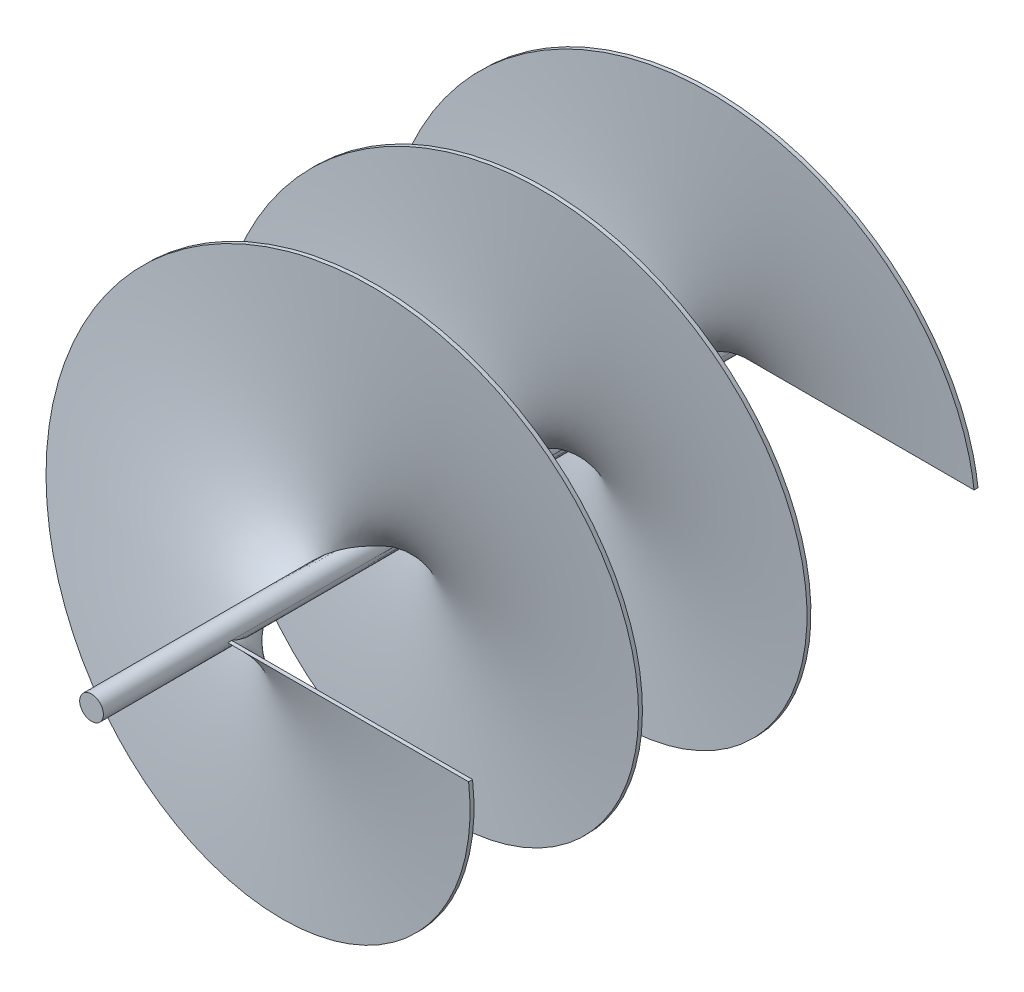
SolidWorks part; units mm, degrees
material "Plain Carbon Steel"
ref_plane "Front Plane" through (0, 0, 0) normal (0, 0, 1) x (1, 0, 0)
ref_plane "Top Plane" through (0, 0, 0) normal (0, 1, 0) x (1, 0, 0)
ref_plane "Right Plane" through (0, 0, 0) normal (1, 0, 0) x (0, 0, -1)
sketch "Sketch1" plane through (0, 0, 0) normal (0, 0, 1) x (1, 0, 0)
  circle A0 centre (0, 0) radius 9.525
  dimension "D1" = 19.05
extrude "Boss-Extrude1" add sketch "Sketch1" along normal blind 609.6
ref_plane "Plane1" through (0, 0, 508) normal (0, 0, 1) x (1, 0, 0)
sketch "Sketch2" plane through (0, 0, 508) normal (0, 0, 1) x (1, 0, 0)
  circle A0 centre (0, 0) radius 203.2
  dimension "D1" = 406.4
curve "Helix/Spiral1" pitch 135.4667 height 406.4 radius 203.2 centre (0, 0, 508) axis (0, 0, -1) start towards (1, 0, 0)
sketch "Sketch3" plane through (0, 0, 0) normal (0, 1, 0) x (1, 0, 0)
  line L0 (-9.525, 0) -> (-9.525, -609.6) construction
  line L1 (-9.525, -509.5875) -> (203.2, -509.5875)
  line L2 (-9.525, -509.5875) -> (-9.525, -506.4125)
  line L3 (-9.525, -506.4125) -> (203.2, -506.4125)
  line L4 (203.2, -509.5875) -> (203.2, -506.4125)
  spline S0 degree 3 poles (-795.7118, -553.8828) (-91.6333, -551.3817) (233.2801, -527.8361) (199.5403, -503.7221) (194.5854, -501.5831) (187.717, -499.4442) (179.0025, -497.3053) (168.5276, -495.1663) (156.3954, -493.0274) (142.7252, -490.8884) (127.6515, -488.7495) (111.3223, -486.6105) (93.8984, -484.4716) (75.5511, -482.3326) (56.4608, -480.1937) (36.8153, -478.0547) (16.8077, -475.9158) (-3.3652, -473.7768) (-23.505, -471.6379) (-43.4136, -469.4989) (-62.8953, -467.36) (-81.7585, -465.2211) (-99.8177, -463.0821) (-116.8952, -460.9432) (-132.8231, -458.8042) (-147.4449, -456.6653) (-160.6166, -454.5263) (-172.2088, -452.3874) (-182.1075, -450.2484) (-190.2153, -448.1095) (-196.4524, -445.9705) (-200.7577, -443.8316) (-203.0886, -441.6926) (-203.4223, -439.5537) (-201.7555, -437.4147) (-198.1047, -435.2758) (-192.5056, -433.1368) (-185.0134, -430.9979) (-175.7017, -428.8589) (-164.6621, -426.72) (-152.0033, -424.5811) (-137.8496, -422.4421) (-122.3402, -420.3032) (-105.6277, -418.1642) (-87.8765, -416.0253) (-69.2611, -413.8863) (-49.9645, -411.7474) (-30.1766, -409.6084) (-10.092, -407.4695) (10.092, -405.3305) (30.1766, -403.1916) (49.9645, -401.0526) (69.2611, -398.9137) (87.8765, -396.7747) (105.6277, -394.6358) (122.3402, -392.4968) (137.8496, -390.3579) (152.0033, -388.2189) (164.6621, -386.08) (175.7017, -383.9411) (185.0134, -381.8021) (192.5056, -379.6632) (198.1047, -377.5242) (201.7555, -375.3853) (203.4223, -373.2463) (203.0886, -371.1074) (200.7577, -368.9684) (196.4524, -366.8295) (190.2153, -364.6905) (182.1075, -362.5516) (172.2088, -360.4126) (160.6166, -358.2737) (147.4449, -356.1347) (132.8231, -353.9958) (116.8952, -351.8568) (99.8177, -349.7179) (81.7585, -347.5789) (62.8953, -345.44) (43.4136, -343.3011) (23.505, -341.1621) (3.3652, -339.0232) (-16.8077, -336.8842) (-36.8153, -334.7453) (-56.4608, -332.6063) (-75.5511, -330.4674) (-93.8984, -328.3284) (-111.3223, -326.1895) (-127.6515, -324.0505) (-142.7252, -321.9116) (-156.3954, -319.7726) (-168.5276, -317.6337) (-179.0025, -315.4947) (-187.717, -313.3558) (-194.5854, -311.2168) (-199.5403, -309.0779) (-202.5328, -306.9389) (-203.5336, -304.8) (-202.5328, -302.6611) (-199.5403, -300.5221) (-194.5854, -298.3832) (-187.717, -296.2442) (-179.0025, -294.1053) (-168.5276, -291.9663) (-156.3954, -289.8274) (-142.7252, -287.6884) (-127.6515, -285.5495) (-111.3223, -283.4105) (-93.8984, -281.2716) (-75.5511, -279.1326) (-56.4608, -276.9937) (-36.8153, -274.8547) (-16.8077, -272.7158) (3.3652, -270.5768) (23.505, -268.4379) (43.4136, -266.2989) (62.8953, -264.16) (81.7585, -262.0211) (99.8177, -259.8821) (116.8952, -257.7432) (132.8231, -255.6042) (147.4449, -253.4653) (160.6166, -251.3263) (172.2088, -249.1874) (182.1075, -247.0484) (190.2153, -244.9095) (196.4524, -242.7705) (200.7577, -240.6316) (203.0886, -238.4926) (203.4223, -236.3537) (201.7555, -234.2147) (198.1047, -232.0758) (192.5056, -229.9368) (185.0134, -227.7979) (175.7017, -225.6589) (164.6621, -223.52) (152.0033, -221.3811) (137.8496, -219.2421) (122.3402, -217.1032) (105.6277, -214.9642) (87.8765, -212.8253) (69.2611, -210.6863) (49.9645, -208.5474) (30.1766, -206.4084) (10.092, -204.2695) (-10.092, -202.1305) (-30.1766, -199.9916) (-49.9645, -197.8526) (-69.2611, -195.7137) (-87.8765, -193.5747) (-105.6277, -191.4358) (-122.3402, -189.2968) (-137.8496, -187.1579) (-152.0033, -185.0189) (-164.6621, -182.88) (-175.7017, -180.7411) (-185.0134, -178.6021) (-192.5056, -176.4632) (-198.1047, -174.3242) (-201.7555, -172.1853) (-203.4223, -170.0463) (-203.0886, -167.9074) (-200.7577, -165.7684) (-196.4524, -163.6295) (-190.2153, -161.4905) (-182.1075, -159.3516) (-172.2088, -157.2126) (-160.6166, -155.0737) (-147.4449, -152.9347) (-132.8231, -150.7958) (-116.8952, -148.6568) (-99.8177, -146.5179) (-81.7585, -144.3789) (-62.8953, -142.24) (-43.4136, -140.1011) (-23.505, -137.9621) (-3.3652, -135.8232) (16.8077, -133.6842) (36.8153, -131.5453) (56.4608, -129.4063) (75.5511, -127.2674) (93.8984, -125.1284) (111.3223, -122.9895) (127.6515, -120.8505) (142.7252, -118.7116) (156.3954, -116.5726) (168.5276, -114.4337) (179.0025, -112.2947) (187.717, -110.1558) (194.5854, -108.0169) (199.5403, -105.8779) (233.2791, -81.7646) (-91.612, -58.2198) (-795.6403, -55.7175) knots -0.162231 -0.162231 -0.162231 -0.162231 0.005263 0.010526 0.015789 0.021053 0.026316 0.031579 0.036842 0.042105 0.047368 0.052632 0.057895 0.063158 0.068421 0.073684 0.078947 0.084211 0.089474 0.094737 0.1 0.105263 0.110526 0.115789 0.121053 0.126316 0.131579 0.136842 0.142105 0.147368 0.152632 0.157895 0.163158 0.168421 0.173684 0.178947 0.184211 0.189474 0.194737 0.2 0.205263 0.210526 0.215789 0.221053 0.226316 0.231579 0.236842 0.242105 0.247368 0.252632 0.257895 0.263158 0.268421 0.273684 0.278947 0.284211 0.289474 0.294737 0.3 0.305263 0.310526 0.315789 0.321053 0.326316 0.331579 0.336842 0.342105 0.347368 0.352632 0.357895 0.363158 0.368421 0.373684 0.378947 0.384211 0.389474 0.394737 0.4 0.405263 0.410526 0.415789 0.421053 0.426316 0.431579 0.436842 0.442105 0.447368 0.452632 0.457895 0.463158 0.468421 0.473684 0.478947 0.484211 0.489474 0.494737 0.5 0.505263 0.510526 0.515789 0.521053 0.526316 0.531579 0.536842 0.542105 0.547368 0.552632 0.557895 0.563158 0.568421 0.573684 0.578947 0.584211 0.589474 0.594737 0.6 0.605263 0.610526 0.615789 0.621053 0.626316 0.631579 0.636842 0.642105 0.647368 0.652632 0.657895 0.663158 0.668421 0.673684 0.678947 0.684211 0.689474 0.694737 0.7 0.705263 0.710526 0.715789 0.721053 0.726316 0.731579 0.736842 0.742105 0.747368 0.752632 0.757895 0.763158 0.768421 0.773684 0.778947 0.784211 0.789474 0.794737 0.8 0.805263 0.810526 0.815789 0.821053 0.826316 0.831579 0.836842 0.842105 0.847368 0.852632 0.857895 0.863158 0.868421 0.873684 0.878947 0.884211 0.889474 0.894737 0.9 0.905263 0.910526 0.915789 0.921053 0.926316 0.931579 0.936842 0.942105 0.947368 0.952632 0.957895 0.963158 0.968421 0.973684 0.978947 0.984211 0.989474 0.994737 1.162226 1.162226 1.162226 1.162226 only from (203.2, -508) to (203.2, -101.6) construction
  spline S1 degree 3 poles (203.2, -508) (203.2, -507.2873) (202.5328, -505.8609) (199.5403, -503.7221) (194.5854, -501.5831) (187.717, -499.4442) (179.0025, -497.3053) (168.5276, -495.1663) (156.3954, -493.0274) (142.7252, -490.8884) (127.6515, -488.7495) (111.3223, -486.6105) (93.8984, -484.4716) (75.5511, -482.3326) (56.4608, -480.1937) (36.8153, -478.0547) (16.8077, -475.9158) (-3.3652, -473.7768) (-23.505, -471.6379) (-43.4136, -469.4989) (-62.8953, -467.36) (-81.7585, -465.2211) (-99.8177, -463.0821) (-116.8952, -460.9432) (-132.8231, -458.8042) (-147.4449, -456.6653) (-160.6166, -454.5263) (-172.2088, -452.3874) (-182.1075, -450.2484) (-190.2153, -448.1095) (-196.4524, -445.9705) (-200.7577, -443.8316) (-203.0886, -441.6926) (-203.4223, -439.5537) (-201.7555, -437.4147) (-198.1047, -435.2758) (-192.5056, -433.1368) (-185.0134, -430.9979) (-175.7017, -428.8589) (-164.6621, -426.72) (-152.0033, -424.5811) (-137.8496, -422.4421) (-122.3402, -420.3032) (-105.6277, -418.1642) (-87.8765, -416.0253) (-69.2611, -413.8863) (-49.9645, -411.7474) (-30.1766, -409.6084) (-10.092, -407.4695) (10.092, -405.3305) (30.1766, -403.1916) (49.9645, -401.0526) (69.2611, -398.9137) (87.8765, -396.7747) (105.6277, -394.6358) (122.3402, -392.4968) (137.8496, -390.3579) (152.0033, -388.2189) (164.6621, -386.08) (175.7017, -383.9411) (185.0134, -381.8021) (192.5056, -379.6632) (198.1047, -377.5242) (201.7555, -375.3853) (203.4223, -373.2463) (203.0886, -371.1074) (200.7577, -368.9684) (196.4524, -366.8295) (190.2153, -364.6905) (182.1075, -362.5516) (172.2088, -360.4126) (160.6166, -358.2737) (147.4449, -356.1347) (132.8231, -353.9958) (116.8952, -351.8568) (99.8177, -349.7179) (81.7585, -347.5789) (62.8953, -345.44) (43.4136, -343.3011) (23.505, -341.1621) (3.3652, -339.0232) (-16.8077, -336.8842) (-36.8153, -334.7453) (-56.4608, -332.6063) (-75.5511, -330.4674) (-93.8984, -328.3284) (-111.3223, -326.1895) (-127.6515, -324.0505) (-142.7252, -321.9116) (-156.3954, -319.7726) (-168.5276, -317.6337) (-179.0025, -315.4947) (-187.717, -313.3558) (-194.5854, -311.2168) (-199.5403, -309.0779) (-202.5328, -306.9389) (-203.5336, -304.8) (-202.5328, -302.6611) (-199.5403, -300.5221) (-194.5854, -298.3832) (-187.717, -296.2442) (-179.0025, -294.1053) (-168.5276, -291.9663) (-156.3954, -289.8274) (-142.7252, -287.6884) (-127.6515, -285.5495) (-111.3223, -283.4105) (-93.8984, -281.2716) (-75.5511, -279.1326) (-56.4608, -276.9937) (-36.8153, -274.8547) (-16.8077, -272.7158) (3.3652, -270.5768) (23.505, -268.4379) (43.4136, -266.2989) (62.8953, -264.16) (81.7585, -262.0211) (99.8177, -259.8821) (116.8952, -257.7432) (132.8231, -255.6042) (147.4449, -253.4653) (160.6166, -251.3263) (172.2088, -249.1874) (182.1075, -247.0484) (190.2153, -244.9095) (196.4524, -242.7705) (200.7577, -240.6316) (203.0886, -238.4926) (203.4223, -236.3537) (201.7555, -234.2147) (198.1047, -232.0758) (192.5056, -229.9368) (185.0134, -227.7979) (175.7017, -225.6589) (164.6621, -223.52) (152.0033, -221.3811) (137.8496, -219.2421) (122.3402, -217.1032) (105.6277, -214.9642) (87.8765, -212.8253) (69.2611, -210.6863) (49.9645, -208.5474) (30.1766, -206.4084) (10.092, -204.2695) (-10.092, -202.1305) (-30.1766, -199.9916) (-49.9645, -197.8526) (-69.2611, -195.7137) (-87.8765, -193.5747) (-105.6277, -191.4358) (-122.3402, -189.2968) (-137.8496, -187.1579) (-152.0033, -185.0189) (-164.6621, -182.88) (-175.7017, -180.7411) (-185.0134, -178.6021) (-192.5056, -176.4632) (-198.1047, -174.3242) (-201.7555, -172.1853) (-203.4223, -170.0463) (-203.0886, -167.9074) (-200.7577, -165.7684) (-196.4524, -163.6295) (-190.2153, -161.4905) (-182.1075, -159.3516) (-172.2088, -157.2126) (-160.6166, -155.0737) (-147.4449, -152.9347) (-132.8231, -150.7958) (-116.8952, -148.6568) (-99.8177, -146.5179) (-81.7585, -144.3789) (-62.8953, -142.24) (-43.4136, -140.1011) (-23.505, -137.9621) (-3.3652, -135.8232) (16.8077, -133.6842) (36.8153, -131.5453) (56.4608, -129.4063) (75.5511, -127.2674) (93.8984, -125.1284) (111.3223, -122.9895) (127.6515, -120.8505) (142.7252, -118.7116) (156.3954, -116.5726) (168.5276, -114.4337) (179.0025, -112.2947) (187.717, -110.1558) (194.5854, -108.0169) (199.5403, -105.8779) (202.5328, -103.7391) (203.2, -102.3127) (203.2, -101.6) knots 0 0 0 0 0.005263 0.010526 0.015789 0.021053 0.026316 0.031579 0.036842 0.042105 0.047368 0.052632 0.057895 0.063158 0.068421 0.073684 0.078947 0.084211 0.089474 0.094737 0.1 0.105263 0.110526 0.115789 0.121053 0.126316 0.131579 0.136842 0.142105 0.147368 0.152632 0.157895 0.163158 0.168421 0.173684 0.178947 0.184211 0.189474 0.194737 0.2 0.205263 0.210526 0.215789 0.221053 0.226316 0.231579 0.236842 0.242105 0.247368 0.252632 0.257895 0.263158 0.268421 0.273684 0.278947 0.284211 0.289474 0.294737 0.3 0.305263 0.310526 0.315789 0.321053 0.326316 0.331579 0.336842 0.342105 0.347368 0.352632 0.357895 0.363158 0.368421 0.373684 0.378947 0.384211 0.389474 0.394737 0.4 0.405263 0.410526 0.415789 0.421053 0.426316 0.431579 0.436842 0.442105 0.447368 0.452632 0.457895 0.463158 0.468421 0.473684 0.478947 0.484211 0.489474 0.494737 0.5 0.505263 0.510526 0.515789 0.521053 0.526316 0.531579 0.536842 0.542105 0.547368 0.552632 0.557895 0.563158 0.568421 0.573684 0.578947 0.584211 0.589474 0.594737 0.6 0.605263 0.610526 0.615789 0.621053 0.626316 0.631579 0.636842 0.642105 0.647368 0.652632 0.657895 0.663158 0.668421 0.673684 0.678947 0.684211 0.689474 0.694737 0.7 0.705263 0.710526 0.715789 0.721053 0.726316 0.731579 0.736842 0.742105 0.747368 0.752632 0.757895 0.763158 0.768421 0.773684 0.778947 0.784211 0.789474 0.794737 0.8 0.805263 0.810526 0.815789 0.821053 0.826316 0.831579 0.836842 0.842105 0.847368 0.852632 0.857895 0.863158 0.868421 0.873684 0.878947 0.884211 0.889474 0.894737 0.9 0.905263 0.910526 0.915789 0.921053 0.926316 0.931579 0.936842 0.942105 0.947368 0.952632 0.957895 0.963158 0.968421 0.973684 0.978947 0.984211 0.989474 0.994737 1 1 1 1 construction
  point P8 (203.2, -508)
  dimension "D1" = 3.175
sweep "Sweep1" add profiles "Sketch3" path "Helix/Spiral1"
